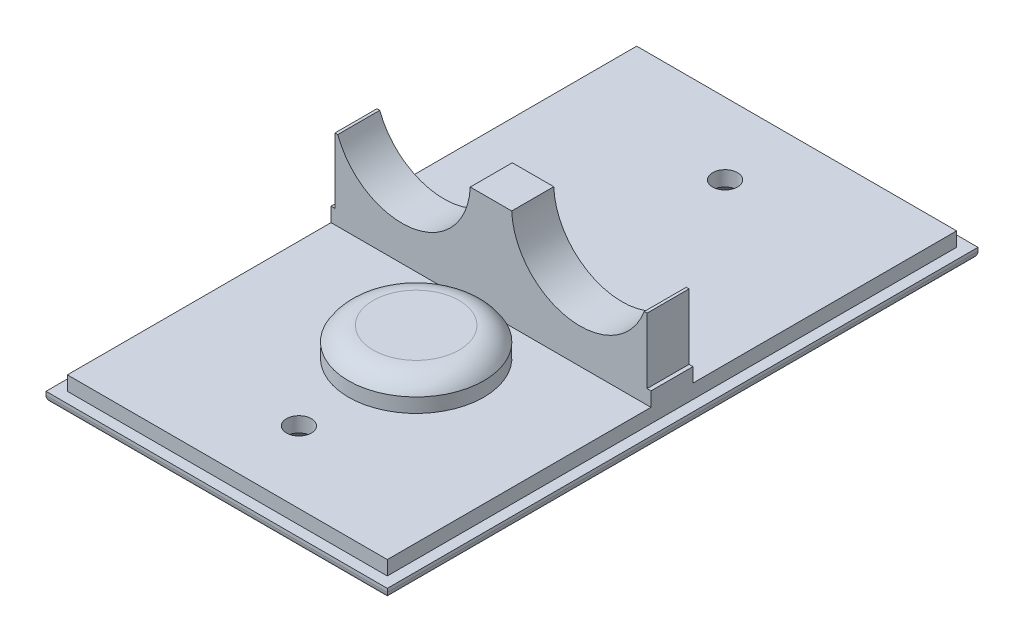
SolidWorks part; units mm, degrees
ref_plane "Спереди" through (0, 0, 0) normal (0, 0, 1) x (1, 0, 0)
ref_plane "Сверху" through (0, 0, 0) normal (0, 1, 0) x (1, 0, 0)
ref_plane "Справа" through (0, 0, 0) normal (1, 0, 0) x (0, 0, -1)
sketch "Эскиз1" plane through (0, 0, 0) normal (0, 1, 0) x (1, 0, 0)
  line L1 (22.45, -39.95) -> (-22.45, -39.95)
  line L2 (22.45, -39.95) -> (22.45, 39.95)
  line L3 (22.45, 39.95) -> (-22.45, 39.95)
  line L4 (-22.45, -39.95) -> (-22.45, 39.95)
  line L5 (22.45, -39.95) -> (-22.45, 39.95) construction
  line L6 (22.45, 39.95) -> (-22.45, -39.95) construction
  point P0 (0, 0)
  dimension "D1" = 79.9
  dimension "D2" = 44.9
extrude "Бобышка-Вытянуть1" add sketch "Эскиз1" along normal blind 4
sketch "Эскиз2" plane through (0, 4, 0) normal (0, 1, 0) x (1, 0, 0)
  line L0 (-22.45, -39.95) -> (22.45, -39.95) construction
  line L1 (21.9, -2.95) -> (-21.9, -2.95)
  line L2 (21.9, -2.95) -> (21.9, 2.95)
  line L3 (21.9, 2.95) -> (-21.9, 2.95)
  line L4 (-21.9, -2.95) -> (-21.9, 2.95)
  line L5 (21.9, -2.95) -> (-21.9, 2.95) construction
  line L6 (21.9, 2.95) -> (-21.9, -2.95) construction
  point P0 (0, 0)
  point P6 (-21.9, 0)
  point P7 (21.9, 0)
  point P8 (0, -2.95)
  point P11 (0, -39.95)
  dimension "D1" = 43.8
  dimension "D2" = 37
extrude "Бобышка-Вытянуть2" add sketch "Эскиз2" along normal blind 12.5
sketch "Эскиз3" plane through (0, 0, 2.95) normal (0, 0, 1) x (1, 0, 0)
  line L0 (-22.45, 4) -> (22.45, 4) construction
  line L1 (-2.9085, 16.0972) -> (2.9085, 16.0972)
  line L2 (-12.5, 26.1) -> (12.5, 26.1)
  line L3 (-21.5057, 13.1747) -> (-23.5505, 13.1747)
  line L4 (-23.5505, 13.1747) -> (-22.1, 16.5)
  line L5 (-22.1, 16.5) -> (22.1, 4) construction
  line L6 (-22.1, 4) -> (22.1, 16.5) construction
  line L7 (21.5057, 13.1747) -> (23.6495, 13.1747)
  line L8 (23.6495, 13.1747) -> (22.1, 16.5)
  arc A0 (-12.5, 26.1) -> (-22.1, 16.5) centre (-12.5, 16.5) ccw
  arc A1 (2.9085, 16.0972) -> (21.5057, 13.1747) centre (12.5, 16.5) ccw
  arc A2 (-21.5057, 13.1747) -> (-2.9085, 16.0972) centre (-12.5, 16.5) ccw
  arc A3 (22.1, 16.5) -> (12.5, 26.1) centre (12.5, 16.5) ccw
  point P0 (0, 10.25)
  dimension "D2" = 19.2
  dimension "D3" = 19.2
  dimension "D1" = 44.2
extrude "Вырез-Вытянуть6" cut sketch "Эскиз3" against normal through all
sketch "Эскиз7" plane through (0, 4, 0) normal (0, 1, 0) x (1, 0, 0)
  line L0 (0, 39.95) -> (0, -39.95) construction
  line L1 (22.45, 39.95) -> (-22.45, 39.95) construction
  line L2 (-22.45, -39.95) -> (22.45, -39.95) construction
  line L3 (-22.45, 0) -> (22.45, 0) construction
  line L4 (-22.45, 39.95) -> (-22.45, -39.95) construction
  line L5 (22.45, -39.95) -> (22.45, 39.95) construction
  circle A0 centre (0, -29.9) radius 1.75
  circle A1 centre (0, 29.9) radius 1.75
  dimension "D1" = 3.5
  dimension "D3" = 3.5
  dimension "D2" = 29.9
  dimension "D4" = 29.9
extrude "Вырез-Вытянуть7" cut sketch "Эскиз7" against normal through all
sketch "Эскиз8" plane through (0, 0, 0) normal (0, -1, 0) x (1, 0, 0)
  line L0 (-22.45, 39.95) -> (22.45, 39.95) construction
  line L1 (23.95, -41.45) -> (-23.95, -41.45)
  line L2 (23.95, -41.45) -> (23.95, 41.45)
  line L3 (23.95, 41.45) -> (-23.95, 41.45)
  line L4 (-23.95, -41.45) -> (-23.95, 41.45)
  line L5 (23.95, -41.45) -> (-23.95, 41.45) construction
  line L6 (23.95, 41.45) -> (-23.95, -41.45) construction
  line L7 (-22.45, -39.95) -> (-22.45, 39.95) construction
  circle A0 centre (0, 29.9) radius 1.75
  circle A1 centre (0, -29.9) radius 1.75
  point P0 (0, 0)
  point P6 (0, 41.45)
  point P11 (-22.45, 0)
  point P12 (-23.95, 0)
  dimension "D1" = 1.5
  dimension "D2" = 1.5
extrude "Бобышка-Вытянуть3" add sketch "Эскиз8" along normal blind 1.5
fillet "Скругление1" radius 1 4 edges at (0, -1.5, 41.45) (23.95, -1.5, 0) (0, -1.5, -41.45) (-23.95, -1.5, 0)
sketch "Эскиз9" plane through (0, -1.5, 0) normal (0, -1, 0) x (1, 0, 0)
  line L0 (0, 40.45) -> (0, -40.45) construction
  line L1 (22.95, 40.45) -> (-22.95, 40.45) construction
  line L2 (-22.95, -40.45) -> (22.95, -40.45) construction
  line L4 (-23.95, 41.45) -> (23.95, 41.45) construction
  circle A0 centre (0, 13.45) radius 7.5
  point P10 (0, 41.45)
  dimension "D1" = 15
  dimension "D2" = 28
extrude "Вырез-Вытянуть8" cut sketch "Эскиз9" against normal through all
chamfer "Фаска1" distance 1.4 angle 45 2 edges at (0, -1.5, -31.65) (0, -1.5, 28.15)
sketch "Эскиз10" plane through (0, 4, 0) normal (0, 1, 0) x (1, 0, 0)
  line L0 (23.95, 41.45) -> (23.95, -41.45) construction
  line L1 (-23.95, 41.45) -> (23.95, 41.45)
  line L2 (-23.95, 41.45) -> (-23.95, 2.95)
  line L3 (-23.95, 2.95) -> (23.95, 2.95)
  line L4 (23.95, 41.45) -> (23.95, 2.95)
  line L5 (-23.95, -41.45) -> (-23.95, 41.45) construction
  line L6 (23.95, -41.45) -> (-23.95, -41.45)
  line L7 (23.95, -41.45) -> (23.95, -2.95)
  line L8 (23.95, -2.95) -> (-23.95, -2.95)
  line L9 (-23.95, -41.45) -> (-23.95, -2.95)
extrude "Вырез-Вытянуть9" cut sketch "Эскиз10" against normal blind 2
sketch "Эскиз11" plane through (0, 2, 0) normal (0, 1, 0) x (1, 0, 0)
  circle A0 centre (0, -13.45) radius 7.5
extrude "Вытянуть-Тонкостенный1" add sketch "Эскиз11" along normal blind 2 draft 1 thin
sketch "Эскиз12" plane through (0, 4, 0) normal (0, 1, 0) x (1, 0, 0)
  circle A0 centre (0, -13.45) radius 9.5
extrude "Бобышка-Вытянуть4" add sketch "Эскиз12" along normal blind 2
fillet "Скругление2" radius 4 2 edges at (0, 6, 22.95) (0, 4, 20.9849)
sketch "Эскиз13" plane through (0, -1.5, 0) normal (0, -1, 0) x (1, 0, 0)
  line L0 (-11, 20.95) -> (-11, 3.9527)
  line L1 (-11, 3.9527) -> (11, 3.9527)
  line L2 (11, 3.9527) -> (11, 20.95)
  arc A0 (-11, 20.95) -> (11, 20.95) centre (0, 20.95) ccw
  circle A1 centre (0, 13.45) radius 7.5 construction
  circle A2 centre (0, 13.45) radius 7.5 construction
  dimension "D1" = 11
extrude "Бобышка-Вытянуть5" add sketch "Эскиз13" against normal blind 1.5
fillet "Скругление3" radius 1 1 edges at (0, 0, 9.95)
